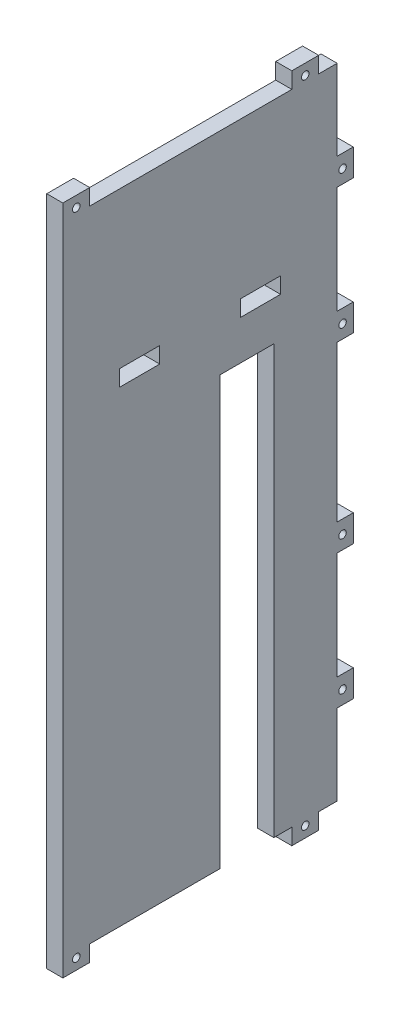
SolidWorks part; units mm, degrees
ref_plane "Plan de face" through (0, 0, 0) normal (0, 0, 1) x (1, 0, 0)
ref_plane "Plan de dessus" through (0, 0, 0) normal (0, 1, 0) x (1, 0, 0)
ref_plane "Plan de droite" through (0, 0, 0) normal (1, 0, 0) x (0, 0, -1)
sketch "Esquisse1" plane through (0, 0, 0) normal (1, 0, 0) x (0, 0, -1)
  line L0 (97.1531, 0) -> (-102.2664, 0) construction
  line L1 (-51.085, 119) -> (51.085, 119)
  line L2 (-51.085, 119) -> (-51.085, -119)
  line L3 (-51.085, -119) -> (51.085, -119)
  line L4 (51.085, 119) -> (51.085, -119)
  line L5 (0, 172.7153) -> (0, -236.1933) construction
  line L15 (-30, 61) -> (-15, 61)
  line L16 (-30, 61) -> (-30, 55)
  line L17 (-30, 55) -> (-15, 55)
  line L18 (-15, 61) -> (-15, 55)
  line L19 (15, 61) -> (30, 61)
  line L20 (15, 61) -> (15, 55)
  line L21 (15, 55) -> (30, 55)
  line L22 (30, 61) -> (30, 55)
  dimension "D1" = 238
  dimension "D2" = 102.17
  dimension "D4" = 119
  dimension "D13" = 15
  dimension "D14" = 15
  dimension "D15" = 30
  dimension "D16" = 6
  dimension "D17" = 6
  dimension "D3" = 51.085
  dimension "D5" = 58
  dimension "D6" = 21.085
extrude "Boss.-Extru.1" add sketch "Esquisse1" along normal blind 6
sketch "Esquisse3" plane through (6, 0, 0) normal (1, 0, 0) x (0, 0, -1)
  line L0 (-51.085, -119) -> (51.085, -119) construction
  line L1 (-51.085, -119) -> (-41.085, -119)
  line L2 (-51.085, -119) -> (-51.085, -125)
  line L3 (-51.085, -125) -> (-41.085, -125)
  line L4 (-41.085, -119) -> (-41.085, -125)
  line L5 (245.3741, 0) -> (-166.5298, 0) construction
  line L6 (51.085, -119) -> (51.085, 119) construction
  line L7 (34.205, -119) -> (44.205, -119)
  line L8 (34.205, -119) -> (34.205, -125)
  line L9 (34.205, -125) -> (44.205, -125)
  line L10 (0, 208.6671) -> (0, -232.3841) construction
  line L12 (44.205, -119) -> (44.205, -125)
  line L13 (51.085, 89) -> (57.085, 89)
  line L14 (51.085, 89) -> (51.085, 79)
  line L15 (51.085, 79) -> (57.085, 79)
  line L16 (57.085, 89) -> (57.085, 79)
  line L17 (51.085, 39) -> (57.085, 39)
  line L18 (51.085, 39) -> (51.085, 29)
  line L19 (51.085, 29) -> (57.085, 29)
  line L20 (57.085, 39) -> (57.085, 29)
  line L21 (57.085, -39) -> (57.085, -29)
  line L22 (51.085, -29) -> (57.085, -29)
  line L23 (51.085, -39) -> (51.085, -29)
  line L24 (51.085, -39) -> (57.085, -39)
  line L25 (57.085, -89) -> (57.085, -79)
  line L26 (51.085, -79) -> (57.085, -79)
  line L27 (51.085, -89) -> (51.085, -79)
  line L28 (51.085, -89) -> (57.085, -89)
  line L29 (0, -208.6671) -> (0, 232.3841) construction
  line L46 (44.205, 119) -> (44.205, 125)
  line L47 (34.205, 125) -> (44.205, 125)
  line L48 (34.205, 119) -> (34.205, 125)
  line L49 (34.205, 119) -> (44.205, 119)
  line L50 (-41.085, 119) -> (-41.085, 125)
  line L51 (-51.085, 125) -> (-41.085, 125)
  line L52 (-51.085, 119) -> (-51.085, 125)
  line L53 (-51.085, 119) -> (-41.085, 119)
  dimension "D2" = 10
  dimension "D3" = 6
  dimension "D4" = 10
  dimension "D5" = 6.88
  dimension "D6" = 6
  dimension "D7" = 10
  dimension "D8" = 6
  dimension "D9" = 6
  dimension "D10" = 10
extrude "Boss.-Extru.5" add sketch "Esquisse3" against normal blind 6
sketch "Esquisse4" plane through (6, 0, 0) normal (1, 0, 0) x (0, 0, -1)
  line L0 (57.085, -29) -> (51.085, -29) construction
  line L1 (57.085, -39) -> (57.085, -29) construction
  line L2 (57.085, -89) -> (57.085, -79) construction
  line L3 (57.085, -79) -> (51.085, -79) construction
  line L10 (-51.085, -125) -> (-41.085, -125) construction
  line L11 (-51.085, 125) -> (-51.085, -125) construction
  line L14 (0, 149.5198) -> (0, -197.2248) construction
  line L15 (203.7475, 0) -> (-122.4342, 0) construction
  line L16 (0, -149.5198) -> (0, 197.2248) construction
  line L17 (34.205, -119) -> (34.205, -125) construction
  line L18 (34.205, -125) -> (44.205, -125) construction
  circle A0 centre (39.205, -121) radius 1.4
  circle A1 centre (53.085, -84) radius 1.4
  circle A2 centre (53.085, -34) radius 1.4
  circle A3 centre (-46.085, 121) radius 1.4
  circle A4 centre (53.085, 34) radius 1.4
  circle A5 centre (53.085, 84) radius 1.4
  circle A8 centre (39.205, 121) radius 1.4
  circle A15 centre (-46.085, -121) radius 1.4
  point P0 (54.085, -29)
  point P35 (34.205, -122)
  dimension "D2" = 2.8
  dimension "D3" = 2.8
  dimension "D4" = 4
  dimension "D5" = 2.8
  dimension "D6" = 5
  dimension "D7" = 5
  dimension "D8" = 4
  dimension "D9" = 4
  dimension "D10" = 2.8
  dimension "D11" = 5
  dimension "D12" = 4
  dimension "D13" = 5
extrude "Enlèv. mat.-Extru.1" cut sketch "Esquisse4" against normal blind 6
sketch "Esquisse6" plane through (6, 0, 0) normal (1, 0, 0) x (0, 0, -1)
  line L0 (-41.085, -119) -> (34.205, -119) construction
  line L1 (7.485, -119) -> (27.485, -119)
  line L2 (7.485, -119) -> (7.485, 40.29)
  line L3 (7.485, 40.29) -> (27.485, 40.29)
  line L4 (27.485, -119) -> (27.485, 40.29)
  line L6 (-41.085, 125) -> (-51.085, 125) construction
  line L7 (-51.085, 125) -> (-51.085, -125) construction
  dimension "D1" = 20
  dimension "D2" = 84.71
  dimension "D3" = 58.57
extrude "Enlèv. mat.-Extru.2" cut sketch "Esquisse6" against normal blind 6
equation "\"D3@Esquisse1\"=\"D2@Esquisse1\"/2"
equation "\"D4@Esquisse1\"=\"D1@Esquisse1\"/2"
